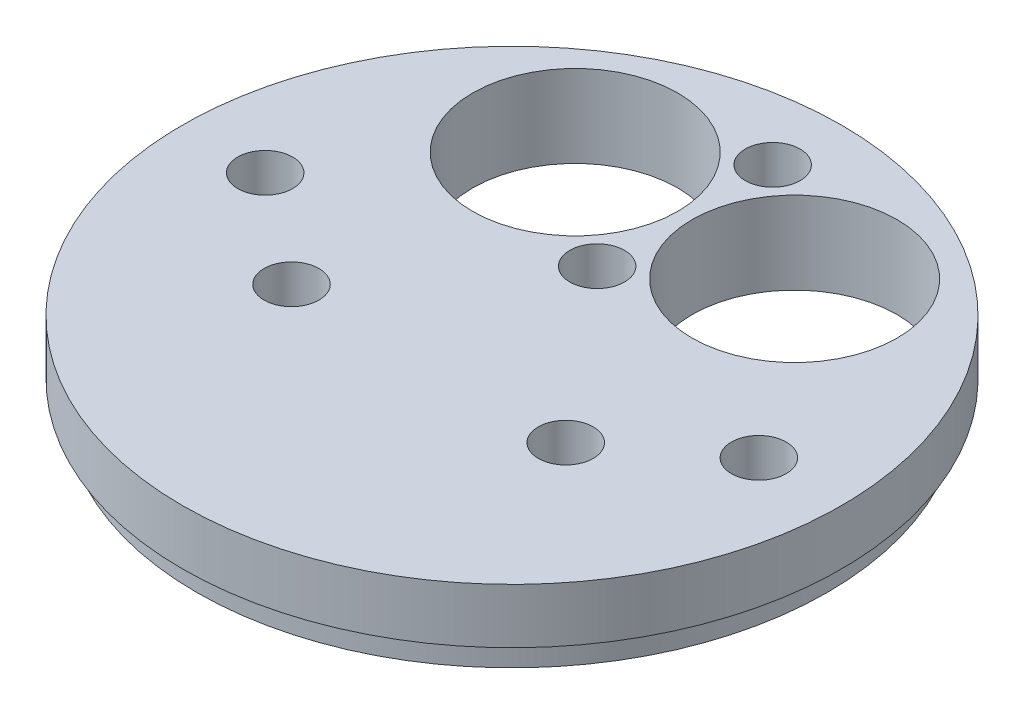
SolidWorks part; units mm, degrees
ref_plane "Front Plane" through (0, 0, 0) normal (0, 0, 1) x (1, 0, 0)
ref_plane "Top Plane" through (0, 0, 0) normal (0, 1, 0) x (1, 0, 0)
ref_plane "Right Plane" through (0, 0, 0) normal (1, 0, 0) x (0, 0, -1)
ref_axis "Axis1" through (0, 55, 0) along (0, -1, 0)
sketch "Sketch1" plane through (0, 0, 0) normal (0, 0, 1) x (1, 0, 0)
  line L0 (0, 0) -> (36.5125, 0)
  line L1 (36.5125, 0) -> (36.5125, 3.175)
  line L2 (36.5125, 3.175) -> (38.1508, 3.175)
  line L3 (38.1508, 3.175) -> (38.1508, 9.525)
  line L4 (38.1508, 9.525) -> (0, 9.525)
  line L5 (0, 55) -> (0, -55) construction
  line L6 (0, 9.525) -> (0, 0)
  line L7 (0, 0) -> (0, 21.2966) construction
  dimension "D1" = 76.3016
  dimension "D2" = 9.525
  dimension "D3" = 73.025
  dimension "D4" = 6.35
revolve "Revolve1" add sketch "Sketch1" angle 360 about L7
sketch "Sketch2" plane through (0, 9.525, 0) normal (0, 1, 0) x (1, 0, 0)
  line L0 (-12.7, 20.0152) -> (12.7, 20.0152) construction
  line L1 (0, 30.1752) -> (0, 9.8552) construction
  line L2 (-12.7, 20.0152) -> (12.7, 20.0152) construction
  line L3 (-12.7, 33.9852) -> (12.7, 33.9852) construction
  line L4 (-12.7, 6.0452) -> (12.7, 6.0452) construction
  circle A0 centre (-12.7, 20.0152) radius 11.8745
  circle A1 centre (0, 0) radius 36.5125
  circle A2 centre (0, 0) radius 36.5125 construction
  circle A3 centre (12.7, 20.0152) radius 11.8745
  circle A4 centre (0, 30.1752) radius 3.175
  circle A5 centre (0, 9.8552) radius 3.175
  arc A6 (-12.7, 33.9852) -> (-12.7, 6.0452) centre (-12.7, 20.0152) ccw construction
  arc A7 (12.7, 6.0452) -> (12.7, 33.9852) centre (12.7, 20.0152) ccw construction
  point P11 (0, 20.0152)
  point P12 (0, 20.0152)
  point P15 (0, 20.0152)
  dimension "D2" = 23.749
  dimension "D3" = 23.749
  dimension "D5" = 6.35
  dimension "D6" = 6.35
  dimension "D4" = 25.4
  dimension "D7" = 20.32
  dimension "D8" = 25.4
  dimension "D9" = 27.94
  dimension "D10" = 20.0152
extrude "Cut-Extrude1" cut sketch "Sketch2" against normal through all both and the other way through all
sketch "Sketch3" plane through (0, 9.525, 0) normal (0, 1, 0) x (1, 0, 0)
  line L0 (-28.575, 0) -> (28.575, 0) construction
  circle A0 centre (-28.575, 0) radius 3.175
  circle A1 centre (28.575, 0) radius 3.175
  point P4 (0, 0)
  dimension "D1" = 6.35
  dimension "D2" = 6.35
  dimension "D3" = 57.15
extrude "Cut-Extrude2" cut sketch "Sketch3" against normal through all both
sketch "Sketch4" plane through (0, 9.525, 0) normal (0, 1, 0) x (1, 0, 0)
  line L0 (15.875, -9.652) -> (-15.875, -9.652) construction
  circle A0 centre (-15.875, -9.652) radius 3.175
  circle A1 centre (15.875, -9.652) radius 3.175
  point P4 (0, -9.652)
  dimension "D2" = 6.35
  dimension "D3" = 6.35
  dimension "D1" = 31.75
  dimension "D4" = 9.652
extrude "Cut-Extrude3" cut sketch "Sketch4" against normal through all both
ref_plane "Plane1" through (0, 4.7625, 0) normal (0, 1, 0) x (-1, 0, 0)
equation "\"D4@Sketch1\"=\"D2@Sketch1\"*(2/3)"
equation "\"D3@Sketch2\"=\"D2@Sketch2\""
equation "\"D6@Sketch2\"=\"D5@Sketch2\""
